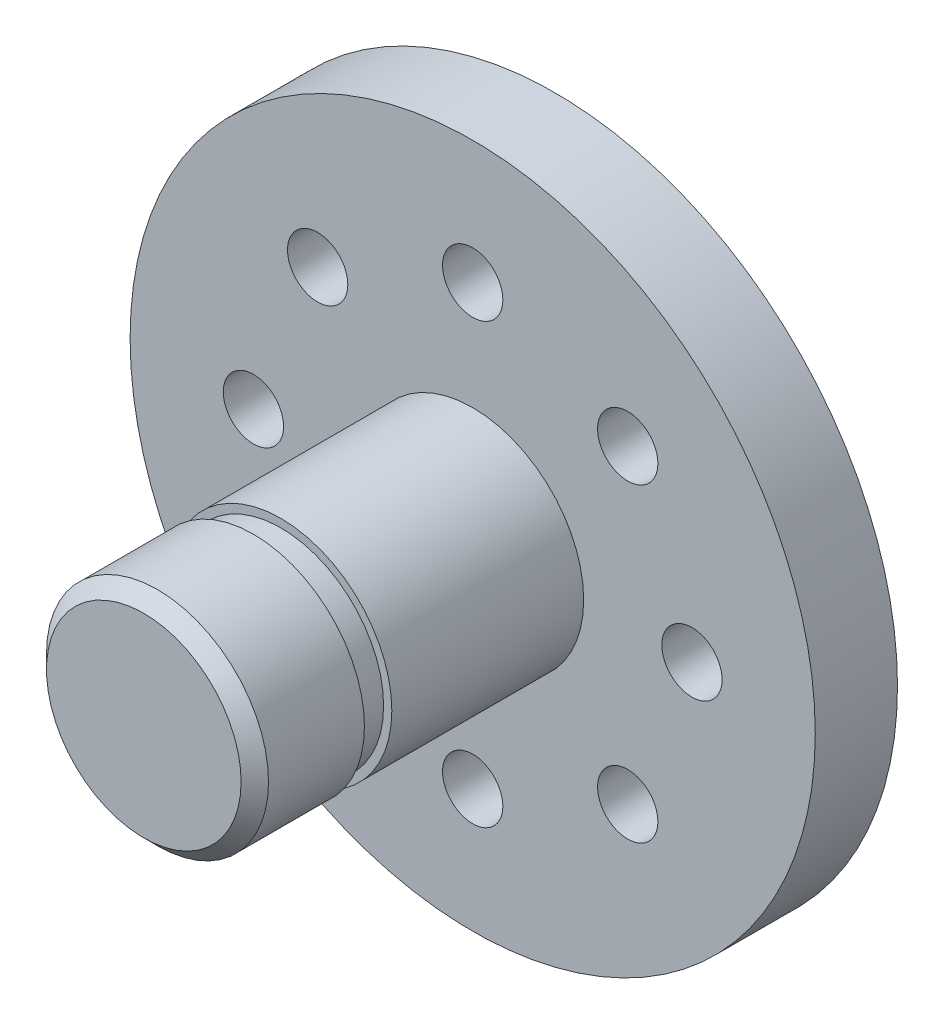
SolidWorks part; units mm, degrees
material "Stainless Steel (ferritic)"
ref_plane "Front Plane" through (0, 0, 0) normal (0, 0, 1) x (1, 0, 0)
ref_plane "Top Plane" through (0, 0, 0) normal (0, 1, 0) x (1, 0, 0)
ref_plane "Right Plane" through (0, 0, 0) normal (1, 0, 0) x (0, 0, -1)
sketch "Sketch1" plane through (0, 0, 0) normal (0, 0, 1) x (1, 0, 0)
  circle A8 centre (0, 0) radius 12.5
  circle A9 centre (0, 8) radius 1.1
  circle A10 centre (5.6569, 5.6569) radius 1.1
  circle A11 centre (8, 0) radius 1.1
  circle A12 centre (5.6569, -5.6569) radius 1.1
  circle A13 centre (0, -8) radius 1.1
  circle A14 centre (-5.6569, -5.6569) radius 1.1
  circle A15 centre (-8, 0) radius 1.1
  circle A16 centre (-5.6569, 5.6569) radius 1.1
  dimension "D1" = 25
  dimension "D2" = 8
  dimension "D3" = 8
extrude "Boss-Extrude1" add sketch "Sketch1" along normal blind 3
sketch "Sketch2" plane through (0, 0, 3) normal (0, 0, 1) x (1, 0, 0)
  circle A0 centre (0, 0) radius 4.05
  dimension "D1" = 8.1
extrude "Boss-Extrude2" add sketch "Sketch2" along normal blind 12
sketch "Sketch3" plane through (0, 0, 0) normal (1, 0, 0) x (0, 0, -1)
  line L0 (-15, 0) -> (0, 0) construction
  line L1 (-15, 4.05) -> (-15, -4.05) construction
  line L2 (-3, 4.05) -> (-15, 4.05) construction
  line L3 (-10, 3.75) -> (-11, 3.75)
  line L4 (-10, 3.75) -> (-10, 4.35)
  line L5 (-10, 4.35) -> (-11, 4.35)
  line L6 (-11, 3.75) -> (-11, 4.35)
  line L7 (-10, 3.75) -> (-11, 4.35) construction
  line L8 (-10, 4.35) -> (-11, 3.75) construction
  line L10 (-3, 12.5) -> (-3, -12.5) construction
  point P5 (-10.5, 4.05)
  dimension "D1" = 1
  dimension "D2" = 0.6
  dimension "D3" = 8
revolve "Cut-Revolve1" cut sketch "Sketch3" angle 360 about L0
fillet "Fillet1" radius 0.5 1 edges at (4.05, 0, 15) profile chamfer
